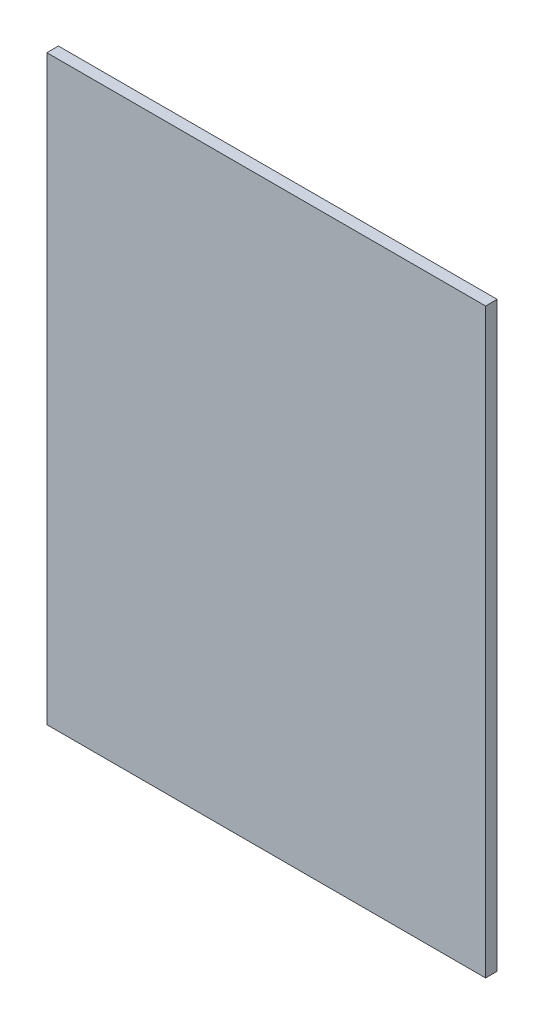
SolidWorks part; units mm, degrees
material "ABS PC"
ref_plane "Plan de face" through (0, 0, 0) normal (0, 0, 1) x (1, 0, 0)
ref_plane "Plan de dessus" through (0, 0, 0) normal (0, 1, 0) x (1, 0, 0)
ref_plane "Plan de droite" through (0, 0, 0) normal (1, 0, 0) x (0, 0, -1)
sketch "Esquisse1" plane through (0, 0, 0) normal (0, 0, 1) x (1, 0, 0)
  line L1 (130, 31.2) -> (320, 31.2)
  line L2 (130, 31.2) -> (130, -220.8)
  line L3 (130, -220.8) -> (320, -220.8)
  line L4 (320, 31.2) -> (320, -220.8)
  line L5 (307, 31.2) -> (7, 31.2) construction
  line L6 (307, -220.8) -> (65.8, -220.8) construction
  line L7 (320, 23.2) -> (320, -222.0619) construction
extrude "Boss.-Extru.1" add sketch "Esquisse1" along normal blind 5
